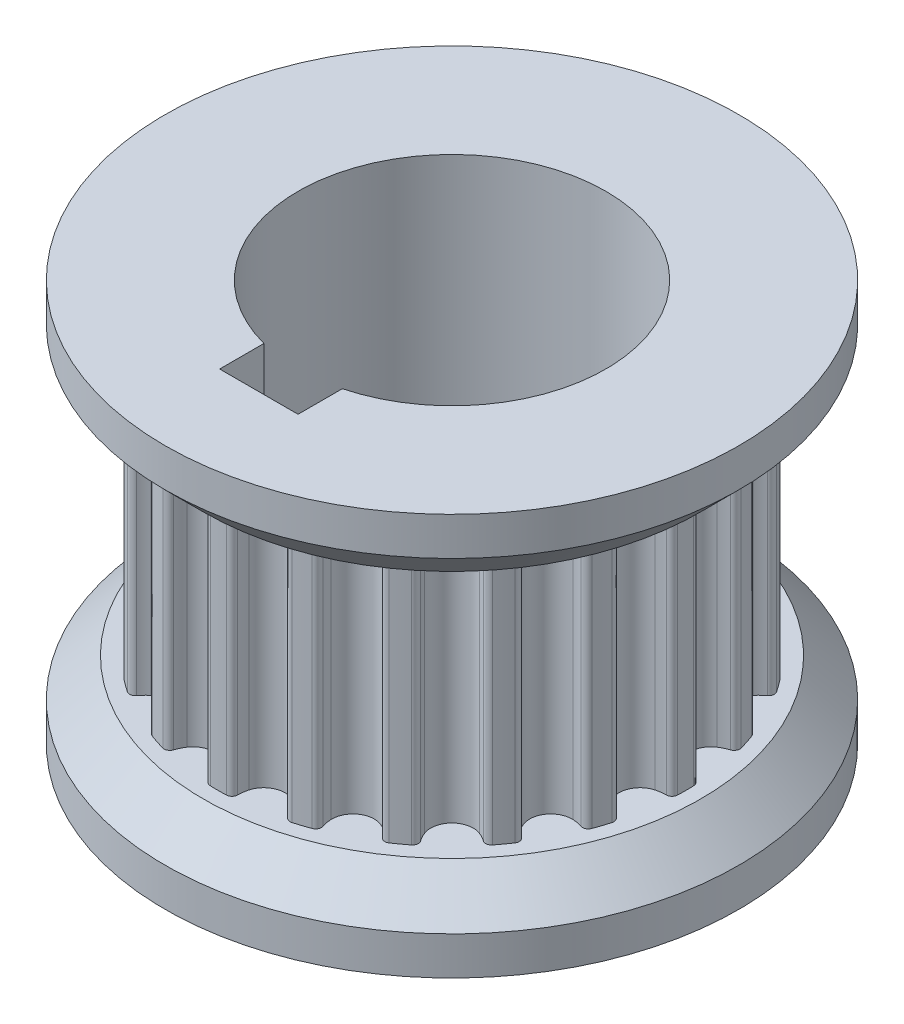
SolidWorks part; units mm, degrees
ref_plane "Plan de face" through (0, 0, 0) normal (0, 0, 1) x (1, 0, 0)
ref_plane "Plan de dessus" through (0, 0, 0) normal (0, 1, 0) x (1, 0, 0)
ref_plane "Plan de droite" through (0, 0, 0) normal (1, 0, 0) x (0, 0, -1)
sketch "Sketch1" plane through (0, 0, 0) normal (0, 1, 0) x (1, 0, 0)
  line L0 (0, 0) -> (0, 6.3662) construction
  line L1 (0, 0) -> (0.9959, 6.2878) construction
  circle A0 centre (0, 0) radius 6.3662 construction
  circle A1 centre (0, 0) radius 6.1122 construction
  circle A2 centre (0, 0) radius 5.3622
  arc A3 (0.3897, 5.7001) -> (0.8388, 5.2962) centre (0.9257, 5.8443) ccw
  arc A4 (0.3897, 5.7001) -> (0.3554, 5.9588) centre (1.3554, 5.96) cw
  arc A5 (-0.2105, 6.1086) -> (0.2105, 6.1086) centre (0, 0) cw
  arc A6 (0.2105, 6.1086) -> (0.3554, 5.9588) centre (0.2054, 5.9587) cw
  arc A7 (-0.3897, 5.7001) -> (-0.8388, 5.2962) centre (-0.9257, 5.8443) cw
  arc A8 (-0.3897, 5.7001) -> (-0.3554, 5.9588) centre (-1.3554, 5.96) ccw
  arc A9 (-0.2105, 6.1086) -> (-0.3554, 5.9588) centre (-0.2054, 5.9587) ccw
  arc A10 (-0.8388, 5.2962) -> (0.8388, 5.2962) centre (0, 0) cw
  dimension "D2" = 12.2244
  dimension "D1" = 12.7324
  dimension "D6" = 0.555
  dimension "D5" = 10.7244
  dimension "D7" = 1
  dimension "D8" = 0.15
  dimension "D3" = 9
extrude "Boss-Extrude1" add sketch "Sketch1" against normal mid plane 6.5 contours A2
extrude "Boss-Extrude2" add sketch "Sketch1<5>" along normal mid plane 6.5 contours A4 A6 A5 A9 A8 A7 A10 A3
sketch "Sketch1<5>" plane through (0, 0, 0) normal (0, 1, 0) x (1, 0, 0) same geometry as "Sketch1"
pattern_circular "CirPattern1" count 20 every 18 about axis through (0, -3.25, 0) along (0, 1, 0) of "Boss-Extrude2" reverse direction yes
sketch "Sketch2" plane through (0, 3.25, 0) normal (0, 1, 0) x (1, 0, 0)
  circle A0 centre (0, 0) radius 7.5
  dimension "D1" = 15
extrude "Boss-Extrude4" add sketch "Sketch2" along normal blind 2 contours A0
sketch "Sketch3" plane through (0, -3.25, 0) normal (0, -1, 0) x (1, 0, 0)
  circle A0 centre (0, 0) radius 7.5
  circle A1 centre (0, 0) radius 7.5 construction
extrude "Boss-Extrude5" add sketch "Sketch3" along normal blind 2
chamfer "Chamfer1" distance 1 angle 45 2 edges at (0, -3.25, -7.5) (0, 3.25, 7.5)
sketch "Sketch4" plane through (0, -5.25, 0) normal (0, -1, 0) x (1, 0, 0)
  line L1 (-1.025, 5.05) -> (1.025, 5.05)
  line L2 (-1.025, 5.05) -> (-1.025, 3)
  line L3 (-1.025, 3) -> (1.025, 3)
  line L4 (1.025, 5.05) -> (1.025, 3)
  line L5 (-1.025, 5.05) -> (1.025, 3) construction
  line L6 (-1.025, 3) -> (1.025, 5.05) construction
  circle A0 centre (0, 0) radius 4.025
  point P3 (0, 4.025)
  dimension "D1" = 8.05
  dimension "D2" = 2.05
  dimension "D3" = 2.05
extrude "Cut-Extrude1" cut sketch "Sketch4" against normal through all contours L2 A0 L4 L3 | A0 L4 L1 L2 | L4 A0 L2 L3 region at (0, -5.25, 4.5148) region at (0, -5.25, 3.4913) region at (0, -5.25, -0.1436)
equation "\"NumTeeth\"= 20"
equation "\"ToothPitch\"= 2mm"
equation "\"PulleyDia\"= \"NumTeeth\" * \"ToothPitch\" / 3.1415926536"
equation "\"ToothAngle\"= 360deg / \"NumTeeth\" * 1deg"
equation "\"TransOffsetAngle\"= \"ToothAngle\" / 5 + 0.001"
equation "\"ShoulderRadius\"= 0.15mm"
equation "\"RootRadius\"= 0.555mm"
equation "\"TransRadius\"= 1mm"
equation "\"PLD\"= 0.254mm"
equation "\"PulleyThickness\"= 6.5"
equation "\"TransOffsetDia\"= \"PulleyDia\" - 0.254 * 2"
equation "\"D1@Sketch1\"=\"PulleyDia\""
equation "\"D2@Sketch1\"=\"TransOffsetDia\""
equation "\"ToothBottomDia\"= \"TransOffsetDia\" - 0.75 * 2"
equation "\"D5@Sketch1\"=\"ToothBottomDia\""
equation "\"D3@Sketch1\"=\"ToothAngle\"/2"
equation "\"D6@Sketch1\"=\"RootRadius\""
equation "\"D7@Sketch1\"=\"TransRadius\""
equation "\"D8@Sketch1\"=\"ShoulderRadius\""
equation "\"D1@Boss-Extrude1\"=\"PulleyThickness\""
equation "\"D2@CirPattern1\"=\"ToothAngle\""
equation "\"D1@CirPattern1\"=\"NumTeeth\""
equation "\"D1@Boss-Extrude2\"=\"PulleyThickness\""
